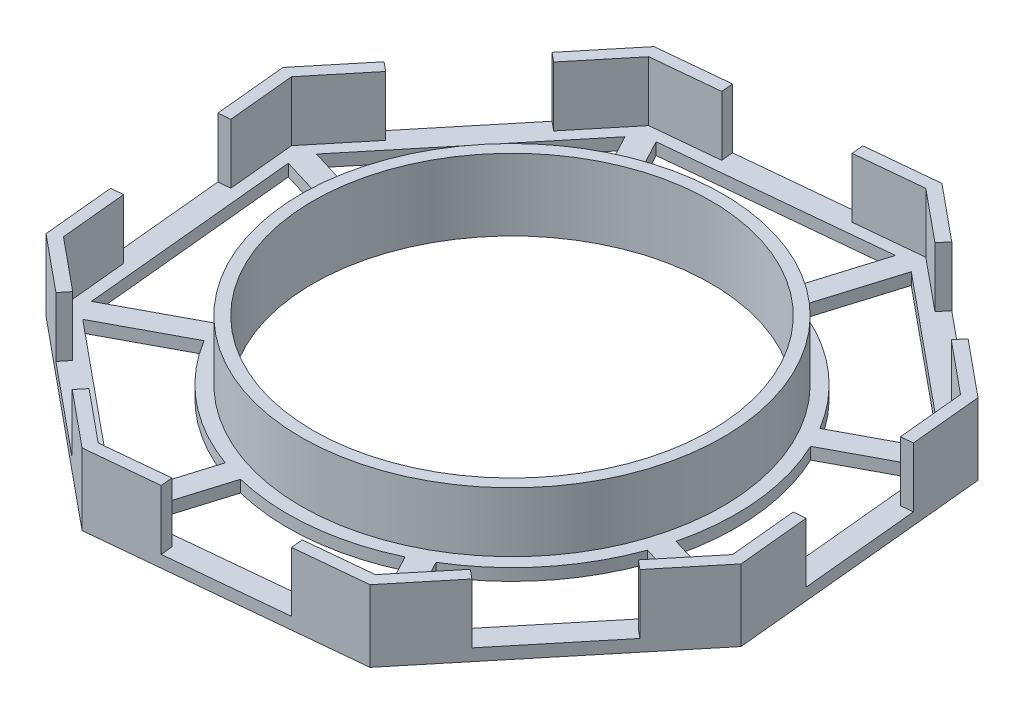
SolidWorks part; units mm, degrees
ref_plane "Front Plane" through (0, 0, 0) normal (0, 0, 1) x (1, 0, 0)
ref_plane "Top Plane" through (0, 0, 0) normal (0, 1, 0) x (1, 0, 0)
ref_plane "Right Plane" through (0, 0, 0) normal (1, 0, 0) x (0, 0, -1)
sketch "Sketch1" plane through (0, 0, 0) normal (0, 1, 0) x (1, 0, 0)
  line L0 (-40.7224, 76.4183) -> (-82.831, 25.2408)
  line L1 (-76.4183, -40.7224) -> (-25.2408, -82.831)
  line L2 (-25.2408, -82.831) -> (40.7224, -76.4183)
  line L3 (40.7224, -76.4183) -> (82.831, -25.2408)
  line L4 (82.831, -25.2408) -> (76.4183, 40.7224)
  line L5 (76.4183, 40.7224) -> (25.2408, 82.831)
  line L6 (25.2408, 82.831) -> (-40.7224, 76.4183)
  line L7 (-82.831, 25.2408) -> (-76.4183, -40.7224)
  circle A0 centre (0, 0) radius 50
  circle A1 centre (0, 0) radius 80 construction
extrude "Boss-Extrude1" add sketch "Sketch1" along normal blind 18
shell "Shell1" thickness 3 removed face at (0, 18, 0)
sketch "Sketch3" plane through (0, 18, 0) normal (0, 1, 0) x (1, 0, 0)
  line L0 (7.1184, 81.0692) -> (7.4087, 78.0833)
  line L1 (25.2408, 82.831) -> (-40.7224, 76.4183) construction
  line L2 (24.2943, 79.7248) -> (-39.1953, 73.5526) construction
  line L3 (7.4087, 78.0833) -> (-22.4505, 75.1804)
  line L4 (-22.4505, 75.1804) -> (-22.7408, 78.1664)
  line L5 (-22.7408, 78.1664) -> (7.1184, 81.0692)
  line L6 (60.4519, 49.9745) -> (37.2857, 69.0355)
  line L7 (62.358, 52.2911) -> (60.4519, 49.9745)
  line L8 (39.1918, 71.3522) -> (62.358, 52.2911)
  line L9 (37.2857, 69.0355) -> (39.1918, 71.3522)
  line L10 (78.0833, -7.4087) -> (75.1804, 22.4505)
  line L11 (81.0692, -7.1184) -> (78.0833, -7.4087)
  line L12 (78.1664, 22.7408) -> (81.0692, -7.1184)
  line L13 (75.1804, 22.4505) -> (78.1664, 22.7408)
  line L14 (49.9745, -60.4519) -> (69.0355, -37.2857)
  line L15 (52.2911, -62.358) -> (49.9745, -60.4519)
  line L16 (71.3522, -39.1918) -> (52.2911, -62.358)
  line L17 (69.0355, -37.2857) -> (71.3522, -39.1918)
  line L18 (-7.4087, -78.0833) -> (22.4505, -75.1804)
  line L19 (-7.1184, -81.0692) -> (-7.4087, -78.0833)
  line L20 (22.7408, -78.1664) -> (-7.1184, -81.0692)
  line L21 (22.4505, -75.1804) -> (22.7408, -78.1664)
  line L22 (-60.4519, -49.9745) -> (-37.2857, -69.0355)
  line L23 (-62.358, -52.2911) -> (-60.4519, -49.9745)
  line L24 (-39.1918, -71.3522) -> (-62.358, -52.2911)
  line L25 (-37.2857, -69.0355) -> (-39.1918, -71.3522)
  line L26 (-78.0833, 7.4087) -> (-75.1804, -22.4505)
  line L27 (-81.0692, 7.1184) -> (-78.0833, 7.4087)
  line L28 (-78.1664, -22.7408) -> (-81.0692, 7.1184)
  line L29 (-75.1804, -22.4505) -> (-78.1664, -22.7408)
  line L30 (-49.9745, 60.4519) -> (-69.0355, 37.2857)
  line L31 (-52.2911, 62.358) -> (-49.9745, 60.4519)
  line L32 (-71.3522, 39.1918) -> (-52.2911, 62.358)
  line L33 (-69.0355, 37.2857) -> (-71.3522, 39.1918)
  point P6 (-7.8112, 79.6178)
  point P39 (6.2491, -1.9043)
  point P41 (0, 0)
  dimension "D1" = 30
  dimension "D2" = 15
  dimension "D3" = 8
extrude "Cut-Extrude1" cut sketch "Sketch3" against normal blind 15
ref_axis "Axis1" through (25.2408, 18, -82.831) along (-0.2915, 0, 0.9566)
ref_axis "Axis2" through (-40.7224, 18, -76.4183) along (0.4703, 0, 0.8825)
sketch "Sketch5" plane through (0, 3, 0) normal (0, 1, 0) x (1, 0, 0)
  line L0 (-34.747, 70.9709) -> (-24.0872, 50.9672)
  line L1 (-40.7224, 76.4183) -> (40.7224, -76.4183) construction
  line L2 (-34.747, 70.9709) -> (20.0799, 76.301)
  line L3 (20.0799, 76.301) -> (13.5067, 54.7304)
  line L4 (25.2408, 82.831) -> (-25.2408, -82.831) construction
  line L5 (7.1184, 81.0692) -> (-22.7408, 78.1664) construction
  line L6 (-22.7408, 78.1664) -> (-22.4505, 75.1804) construction
  line L7 (25.6142, 74.7538) -> (68.1515, 39.7543)
  line L8 (25.6142, 74.7538) -> (19.007, 53.0714)
  line L9 (68.1515, 39.7543) -> (48.2509, 29.1495)
  line L10 (70.9709, 34.747) -> (76.301, -20.0799)
  line L11 (70.9709, 34.747) -> (50.9672, 24.0872)
  line L12 (76.301, -20.0799) -> (54.7304, -13.5067)
  line L13 (74.7538, -25.6142) -> (39.7543, -68.1515)
  line L14 (74.7538, -25.6142) -> (53.0714, -19.007)
  line L15 (39.7543, -68.1515) -> (29.1495, -48.2509)
  line L16 (34.747, -70.9709) -> (-20.0799, -76.301)
  line L17 (34.747, -70.9709) -> (24.0872, -50.9672)
  line L18 (-20.0799, -76.301) -> (-13.5067, -54.7304)
  line L19 (-25.6142, -74.7538) -> (-68.1515, -39.7543)
  line L20 (-25.6142, -74.7538) -> (-19.007, -53.0714)
  line L21 (-68.1515, -39.7543) -> (-48.2509, -29.1495)
  line L22 (-70.9709, -34.747) -> (-76.301, 20.0799)
  line L23 (-70.9709, -34.747) -> (-50.9672, -24.0872)
  line L24 (-76.301, 20.0799) -> (-54.7304, 13.5067)
  line L25 (-74.7538, 25.6142) -> (-39.7543, 68.1515)
  line L26 (-74.7538, 25.6142) -> (-53.0714, 19.007)
  line L27 (-39.7543, 68.1515) -> (-29.1495, 48.2509)
  arc A0 (-24.0872, 50.9672) -> (13.5067, 54.7304) centre (0, 0) cw
  arc A1 (19.007, 53.0714) -> (48.2509, 29.1495) centre (0, 0) cw
  arc A2 (50.9672, 24.0872) -> (54.7304, -13.5067) centre (0, 0) cw
  arc A3 (53.0714, -19.007) -> (29.1495, -48.2509) centre (0, 0) cw
  arc A4 (24.0872, -50.9672) -> (-13.5067, -54.7304) centre (0, 0) cw
  arc A5 (-19.007, -53.0714) -> (-48.2509, -29.1495) centre (0, 0) cw
  arc A6 (-50.9672, -24.0872) -> (-54.7304, 13.5067) centre (0, 0) cw
  arc A7 (-53.0714, 19.007) -> (-29.1495, 48.2509) centre (0, 0) cw
  point P14 (-22.5957, 76.6734)
  point P46 (0, 0)
  dimension "D1" = 4.5
  dimension "D2" = 8
extrude "Cut-Extrude2" cut sketch "Sketch5" against normal through all
